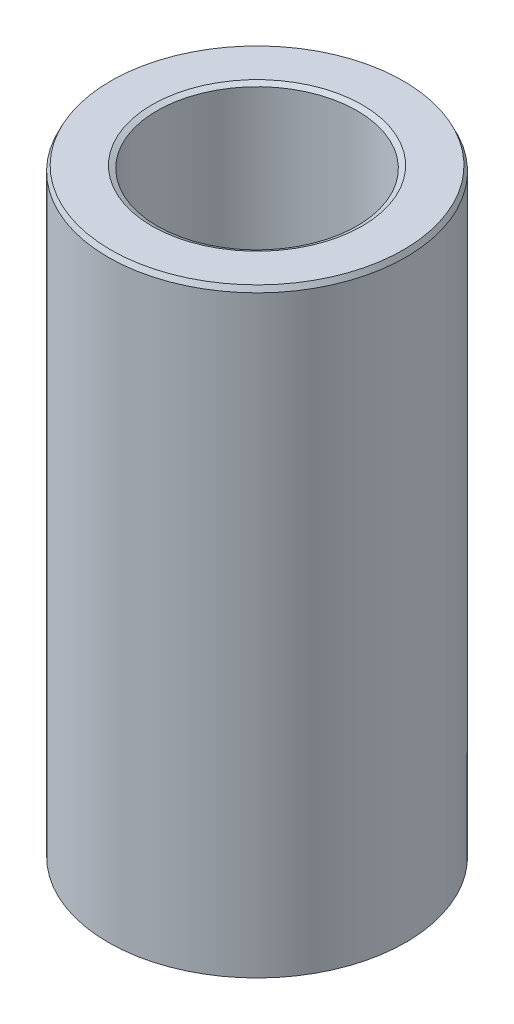
SolidWorks part; units mm, degrees
ref_plane "Front Plane" through (0, 0, 0) normal (0, 0, 1) x (1, 0, 0)
ref_plane "Top Plane" through (0, 0, 0) normal (0, 1, 0) x (1, 0, 0)
ref_plane "Right Plane" through (0, 0, 0) normal (1, 0, 0) x (0, 0, -1)
sketch "Sketch1" plane through (0, 0, 0) normal (0, 1, 0) x (1, 0, 0)
  circle A0 centre (0, 0) radius 50
  dimension "SLEEVE_OD" = 100
extrude "Boss-Extrude1" add sketch "Sketch1" along normal blind 201.8955
sketch "Sketch2" plane through (0, 0, 0) normal (0, 1, 0) x (1, 0, 0)
  circle A0 centre (0, 0) radius 33.5774
  dimension "BORE_D" = 67.1548
extrude "Cut-Extrude1" cut sketch "Sketch2" along normal through all
chamfer "Chamfer1" distance 1.7306 angle 25.95 4 edges at (0, 201.8955, 33.5774) (0, 0, 33.5774) (0, 0, 50) (0, 201.8955, 50) first distance on face at (0, 201.8955, 33.5774) first distance on face at (0, 0, 33.5774) first distance on face at (0, 201.8955, 50)
